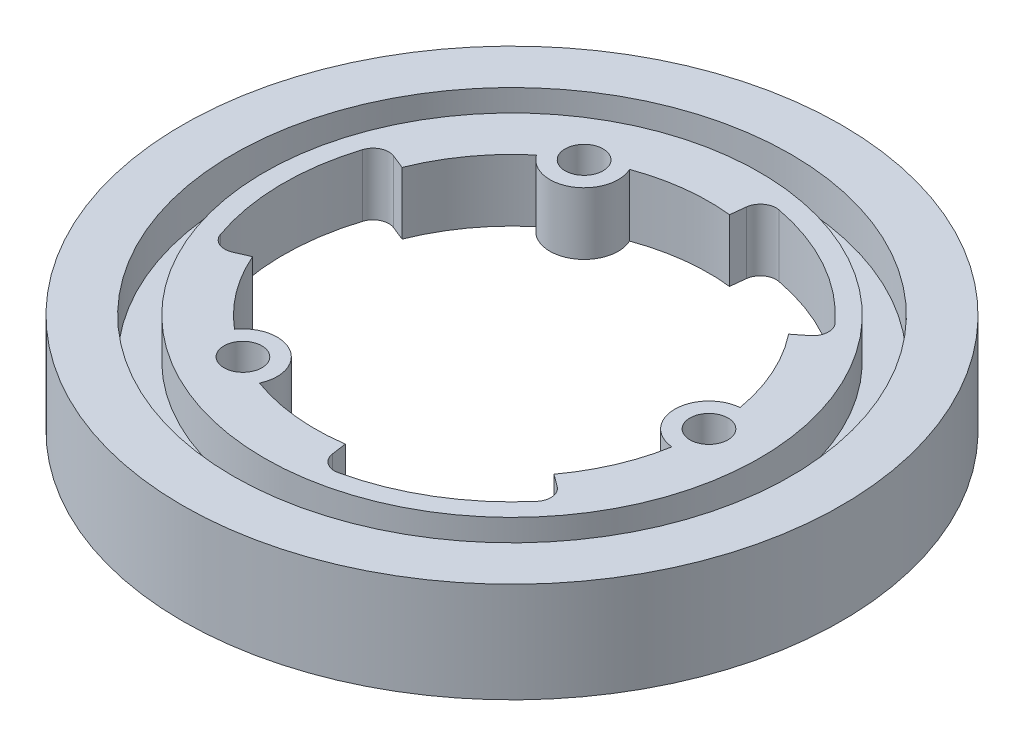
SolidWorks part; units mm, degrees
ref_plane "Front Plane" through (0, 0, 0) normal (0, 0, 1) x (1, 0, 0)
ref_plane "Top Plane" through (0, 0, 0) normal (0, 1, 0) x (1, 0, 0)
ref_plane "Right Plane" through (0, 0, 0) normal (1, 0, 0) x (0, 0, -1)
sketch "Sketch1" plane through (0, 0, 0) normal (0, 1, 0) x (1, 0, 0)
  line L0 (0, 0) -> (1.716, 15.445) construction
  line L1 (0, 0) -> (12.2062, 9.6177) construction
  line L2 (12.2062, 9.6177) -> (1.716, 15.445) construction
  line L3 (12.2062, 9.6177) -> (15.4676, 1.4983) construction
  line L4 (1.716, 15.445) -> (1.8489, 16.641)
  line L5 (12.2062, 9.6177) -> (13.1514, 10.3625)
  line L6 (0, 0) -> (13.5415, 7.6235) construction
  line L7 (13.5415, 7.6235) -> (13.5415, -7.6235) construction
  line L8 (13.5415, -7.6235) -> (0, 0) construction
  line L9 (13.5415, 7.6235) -> (14.5902, 8.2139)
  line L10 (13.5415, -7.6235) -> (14.5902, -8.2139)
  line L11 (0, 0) -> (19.54, 0) construction
  circle A0 centre (0, 0) radius 15.54
  circle A1 centre (0, 0) radius 19.54
  circle A2 centre (0, 0) radius 18.04
  circle A3 centre (0, 0) radius 15.54
  circle A4 centre (15.54, 0) radius 1.5
  circle A5 centre (15.54, 0) radius 2.7
  circle A6 centre (3.0913, 16.503) radius 1.25
  circle A7 centre (12.3778, 11.3443) radius 1.25
  circle A8 centre (15.2034, 7.1246) radius 1.25
  circle A9 centre (15.2034, -7.1246) radius 1.25
  point P24 (13.5415, 0)
  point P27 (19.54, 0)
  dimension "D1" = 31.08
  dimension "D2" = 4
  dimension "D3" = 1.5
  dimension "D4" = 3
  dimension "D5" = 1.2
  dimension "D6" = 12
  dimension "D8" = 2.4
  dimension "D7" = 8.75
extrude "Boss-Extrude1" add sketch "Sketch1" along normal blind 7.9 contours A1 | A0
extrude "Boss-Extrude2" add sketch "Sketch1<3>" along normal up to surface (7.9 mm away) contours A5 up to face at (0, 7.9, 19.54)
sketch "Sketch1<3>" plane through (0, 0, 0) normal (0, 1, 0) x (1, 0, 0) same geometry as "Sketch1"
extrude "Cut-Extrude1" cut sketch "Sketch1<4>" against normal through all both and the other way through all contours A4
sketch "Sketch1<4>" plane through (0, 0, 0) normal (0, 1, 0) x (1, 0, 0) same geometry as "Sketch1"
extrude "Cut-Extrude2" cut sketch "Sketch1<5>" against normal through all both and the other way through all contours A6 L4 A3 | A6 | A7 A2 A6 A3 | A7 | A7 A0 L5 region at (2.0013, 0, -15.6802) region at (3.0913, 0, -16.503) region at (8.0751, 0, -14.5367) region at (12.2552, 0, -9.9842) region at (12.3778, 0, -11.3443)
sketch "Sketch1<5>" plane through (0, 0, 0) normal (0, 1, 0) x (1, 0, 0) same geometry as "Sketch1"
extrude "Cut-Extrude5" cut sketch "Sketch1<6>" along normal blind 3 contours A8 L9 A0 | A8 | A8 A3 A5 A2 | A2 A5 A0 A4 A3 | A9 A2 A5 A3 | A9 | A9 A0 L10 | A5 | A0 region at (13.8991, 0, 7.5292) region at (15.2034, 0, 7.1246) region at (16.3146, 0, 4.2837) region at (15.458, 0, 2.1038) region at (16.3146, 0, -4.2837) region at (15.2034, 0, -7.1246) region at (13.8991, 0, -7.5292)
sketch "Sketch1<6>" plane through (0, 0, 0) normal (0, 1, 0) x (1, 0, 0) same geometry as "Sketch1"
pattern_circular "CirPattern1" count 3 over 360 about axis through (0, 7.9, 0) along (0, -1, 0) of "Boss-Extrude2", "Cut-Extrude1", "Cut-Extrude2", "Cut-Extrude5"
sketch "Sketch2" plane through (0, 0, 0) normal (0, 1, 0) x (1, 0, 0)
  circle A0 centre (0, 0) radius 26
  circle A1 centre (0, 0) radius 19.54
  circle A2 centre (0, 0) radius 22
  circle A3 centre (0, 0) radius 19.54 construction
  dimension "D1" = 52
  dimension "D2" = 4
extrude "Boss-Extrude3" add sketch "Sketch2" along normal up to surface (7.9 mm away) contours A0 | A1 up to face at (-9.069, 7.9, 12.708)
extrude "Cut-Extrude4" cut sketch "Sketch2<3>" against normal blind 3.14 from surface contours A2 | A1 starting at face at (-9.069, 7.9, 12.708)
sketch "Sketch2<3>" plane through (0, 0, 0) normal (0, 1, 0) x (1, 0, 0) same geometry as "Sketch2"
extrude "Cut-Extrude6" cut sketch "Sketch2<4>" along normal blind 3 contours A2
sketch "Sketch2<4>" plane through (0, 0, 0) normal (0, 1, 0) x (1, 0, 0) same geometry as "Sketch2"
